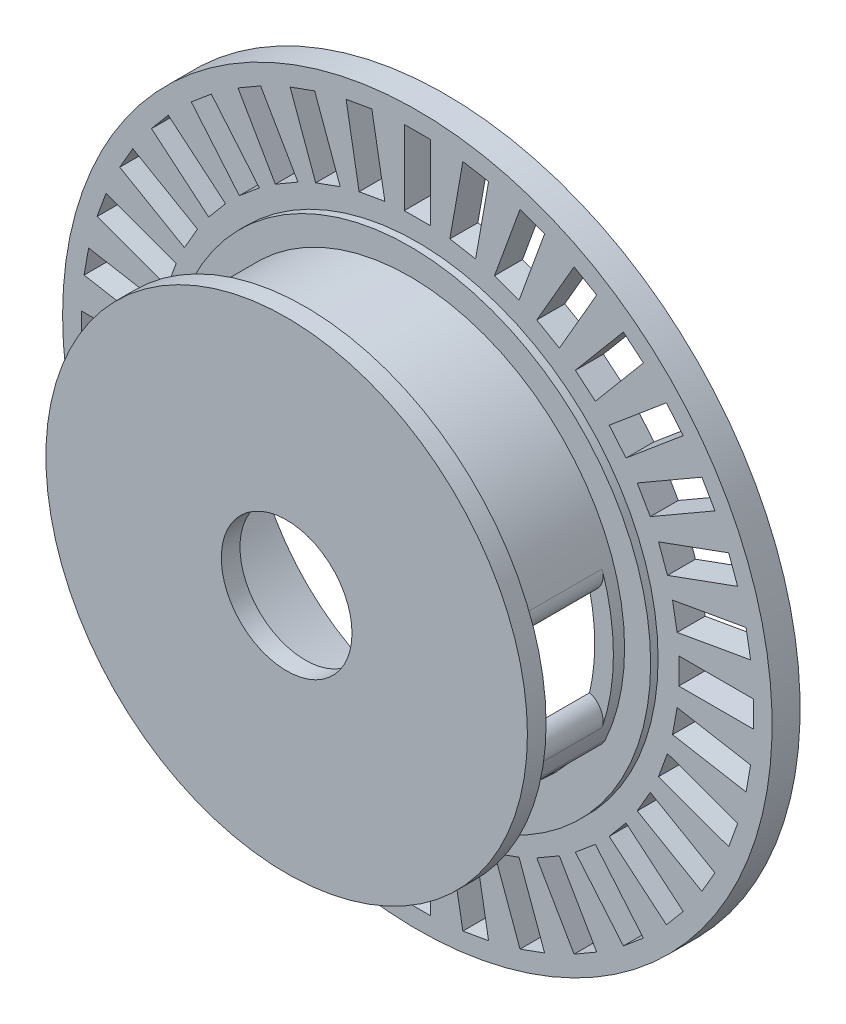
SolidWorks part; units mm, degrees
ref_plane "Front Plane" through (0, 0, 0) normal (0, 0, 1) x (1, 0, 0)
ref_plane "Top Plane" through (0, 0, 0) normal (0, 1, 0) x (1, 0, 0)
ref_plane "Right Plane" through (0, 0, 0) normal (1, 0, 0) x (0, 0, -1)
sketch "Sketch1" plane through (0, 0, 0) normal (0, 0, 1) x (1, 0, 0)
  line L0 (3.1204, 13.6658) -> (1.7417, 13.9089)
  line L1 (0.7, 14) -> (-0.7, 14)
  line L2 (0.7, 14) -> (0.7, 18)
  line L3 (0.7, 18) -> (-0.7, 18)
  line L4 (-0.7, 14) -> (-0.7, 18)
  line L5 (0.7, 14) -> (-0.7, 18) construction
  line L6 (0.7, 18) -> (-0.7, 14) construction
  line L7 (1.7417, 13.9089) -> (2.4363, 17.8481)
  line L8 (3.1204, 13.6658) -> (3.815, 17.605)
  line L9 (3.815, 17.605) -> (2.4363, 17.8481)
  line L10 (5.4461, 12.9163) -> (4.1305, 13.3951)
  line L11 (4.1305, 13.3951) -> (5.4986, 17.1539)
  line L12 (5.4461, 12.9163) -> (6.8141, 16.6751)
  line L13 (6.8141, 16.6751) -> (5.4986, 17.1539)
  line L14 (7.6062, 11.7744) -> (6.3938, 12.4744)
  line L15 (6.3938, 12.4744) -> (8.3938, 15.9385)
  line L16 (7.6062, 11.7744) -> (9.6062, 15.2385)
  line L17 (9.6062, 15.2385) -> (8.3938, 15.9385)
  line L18 (9.5353, 10.2747) -> (8.4628, 11.1746)
  line L19 (8.4628, 11.1746) -> (11.0339, 14.2388)
  line L20 (9.5353, 10.2747) -> (12.1064, 13.3388)
  line L21 (12.1064, 13.3388) -> (11.0339, 14.2388)
  line L22 (11.1746, 8.4628) -> (10.2747, 9.5353)
  line L23 (10.2747, 9.5353) -> (13.3388, 12.1064)
  line L24 (11.1746, 8.4628) -> (14.2388, 11.0339)
  line L25 (14.2388, 11.0339) -> (13.3388, 12.1064)
  line L26 (12.4744, 6.3938) -> (11.7744, 7.6062)
  line L27 (11.7744, 7.6062) -> (15.2385, 9.6062)
  line L28 (12.4744, 6.3938) -> (15.9385, 8.3938)
  line L29 (15.9385, 8.3938) -> (15.2385, 9.6062)
  line L30 (13.3951, 4.1305) -> (12.9163, 5.4461)
  line L31 (12.9163, 5.4461) -> (16.6751, 6.8141)
  line L32 (13.3951, 4.1305) -> (17.1539, 5.4986)
  line L33 (17.1539, 5.4986) -> (16.6751, 6.8141)
  line L34 (13.9089, 1.7417) -> (13.6658, 3.1204)
  line L35 (13.6658, 3.1204) -> (17.605, 3.815)
  line L36 (13.9089, 1.7417) -> (17.8481, 2.4363)
  line L37 (17.8481, 2.4363) -> (17.605, 3.815)
  line L38 (14, -0.7) -> (14, 0.7)
  line L39 (14, 0.7) -> (18, 0.7)
  line L40 (14, -0.7) -> (18, -0.7)
  line L41 (18, -0.7) -> (18, 0.7)
  line L42 (13.6658, -3.1204) -> (13.9089, -1.7417)
  line L43 (13.9089, -1.7417) -> (17.8481, -2.4363)
  line L44 (13.6658, -3.1204) -> (17.605, -3.815)
  line L45 (17.605, -3.815) -> (17.8481, -2.4363)
  line L46 (12.9163, -5.4461) -> (13.3951, -4.1305)
  line L47 (13.3951, -4.1305) -> (17.1539, -5.4986)
  line L48 (12.9163, -5.4461) -> (16.6751, -6.8141)
  line L49 (16.6751, -6.8141) -> (17.1539, -5.4986)
  line L50 (11.7744, -7.6062) -> (12.4744, -6.3938)
  line L51 (12.4744, -6.3938) -> (15.9385, -8.3938)
  line L52 (11.7744, -7.6062) -> (15.2385, -9.6062)
  line L53 (15.2385, -9.6062) -> (15.9385, -8.3938)
  line L54 (10.2747, -9.5353) -> (11.1746, -8.4628)
  line L55 (11.1746, -8.4628) -> (14.2388, -11.0339)
  line L56 (10.2747, -9.5353) -> (13.3388, -12.1064)
  line L57 (13.3388, -12.1064) -> (14.2388, -11.0339)
  line L58 (8.4628, -11.1746) -> (9.5353, -10.2747)
  line L59 (9.5353, -10.2747) -> (12.1064, -13.3388)
  line L60 (8.4628, -11.1746) -> (11.0339, -14.2388)
  line L61 (11.0339, -14.2388) -> (12.1064, -13.3388)
  line L62 (6.3938, -12.4744) -> (7.6062, -11.7744)
  line L63 (7.6062, -11.7744) -> (9.6062, -15.2385)
  line L64 (6.3938, -12.4744) -> (8.3938, -15.9385)
  line L65 (8.3938, -15.9385) -> (9.6062, -15.2385)
  line L66 (4.1305, -13.3951) -> (5.4461, -12.9163)
  line L67 (5.4461, -12.9163) -> (6.8141, -16.6751)
  line L68 (4.1305, -13.3951) -> (5.4986, -17.1539)
  line L69 (5.4986, -17.1539) -> (6.8141, -16.6751)
  line L70 (1.7417, -13.9089) -> (3.1204, -13.6658)
  line L71 (3.1204, -13.6658) -> (3.815, -17.605)
  line L72 (1.7417, -13.9089) -> (2.4363, -17.8481)
  line L73 (2.4363, -17.8481) -> (3.815, -17.605)
  line L74 (-0.7, -14) -> (0.7, -14)
  line L75 (0.7, -14) -> (0.7, -18)
  line L76 (-0.7, -14) -> (-0.7, -18)
  line L77 (-0.7, -18) -> (0.7, -18)
  line L78 (-3.1204, -13.6658) -> (-1.7417, -13.9089)
  line L79 (-1.7417, -13.9089) -> (-2.4363, -17.8481)
  line L80 (-3.1204, -13.6658) -> (-3.815, -17.605)
  line L81 (-3.815, -17.605) -> (-2.4363, -17.8481)
  line L82 (-5.4461, -12.9163) -> (-4.1305, -13.3951)
  line L83 (-4.1305, -13.3951) -> (-5.4986, -17.1539)
  line L84 (-5.4461, -12.9163) -> (-6.8141, -16.6751)
  line L85 (-6.8141, -16.6751) -> (-5.4986, -17.1539)
  line L86 (-7.6062, -11.7744) -> (-6.3938, -12.4744)
  line L87 (-6.3938, -12.4744) -> (-8.3938, -15.9385)
  line L88 (-7.6062, -11.7744) -> (-9.6062, -15.2385)
  line L89 (-9.6062, -15.2385) -> (-8.3938, -15.9385)
  line L90 (-9.5353, -10.2747) -> (-8.4628, -11.1746)
  line L91 (-8.4628, -11.1746) -> (-11.0339, -14.2388)
  line L92 (-9.5353, -10.2747) -> (-12.1064, -13.3388)
  line L93 (-12.1064, -13.3388) -> (-11.0339, -14.2388)
  line L94 (-11.1746, -8.4628) -> (-10.2747, -9.5353)
  line L95 (-10.2747, -9.5353) -> (-13.3388, -12.1064)
  line L96 (-11.1746, -8.4628) -> (-14.2388, -11.0339)
  line L97 (-14.2388, -11.0339) -> (-13.3388, -12.1064)
  line L98 (-12.4744, -6.3938) -> (-11.7744, -7.6062)
  line L99 (-11.7744, -7.6062) -> (-15.2385, -9.6062)
  line L100 (-12.4744, -6.3938) -> (-15.9385, -8.3938)
  line L101 (-15.9385, -8.3938) -> (-15.2385, -9.6062)
  line L102 (-13.3951, -4.1305) -> (-12.9163, -5.4461)
  line L103 (-12.9163, -5.4461) -> (-16.6751, -6.8141)
  line L104 (-13.3951, -4.1305) -> (-17.1539, -5.4986)
  line L105 (-17.1539, -5.4986) -> (-16.6751, -6.8141)
  line L106 (-13.9089, -1.7417) -> (-13.6658, -3.1204)
  line L107 (-13.6658, -3.1204) -> (-17.605, -3.815)
  line L108 (-13.9089, -1.7417) -> (-17.8481, -2.4363)
  line L109 (-17.8481, -2.4363) -> (-17.605, -3.815)
  line L110 (-14, 0.7) -> (-14, -0.7)
  line L111 (-14, -0.7) -> (-18, -0.7)
  line L112 (-14, 0.7) -> (-18, 0.7)
  line L113 (-18, 0.7) -> (-18, -0.7)
  line L114 (-13.6658, 3.1204) -> (-13.9089, 1.7417)
  line L115 (-13.9089, 1.7417) -> (-17.8481, 2.4363)
  line L116 (-13.6658, 3.1204) -> (-17.605, 3.815)
  line L117 (-17.605, 3.815) -> (-17.8481, 2.4363)
  line L118 (-12.9163, 5.4461) -> (-13.3951, 4.1305)
  line L119 (-13.3951, 4.1305) -> (-17.1539, 5.4986)
  line L120 (-12.9163, 5.4461) -> (-16.6751, 6.8141)
  line L121 (-16.6751, 6.8141) -> (-17.1539, 5.4986)
  line L122 (-11.7744, 7.6062) -> (-12.4744, 6.3938)
  line L123 (-12.4744, 6.3938) -> (-15.9385, 8.3938)
  line L124 (-11.7744, 7.6062) -> (-15.2385, 9.6062)
  line L125 (-15.2385, 9.6062) -> (-15.9385, 8.3938)
  line L126 (-10.2747, 9.5353) -> (-11.1746, 8.4628)
  line L127 (-11.1746, 8.4628) -> (-14.2388, 11.0339)
  line L128 (-10.2747, 9.5353) -> (-13.3388, 12.1064)
  line L129 (-13.3388, 12.1064) -> (-14.2388, 11.0339)
  line L130 (-8.4628, 11.1746) -> (-9.5353, 10.2747)
  line L131 (-9.5353, 10.2747) -> (-12.1064, 13.3388)
  line L132 (-8.4628, 11.1746) -> (-11.0339, 14.2388)
  line L133 (-11.0339, 14.2388) -> (-12.1064, 13.3388)
  line L134 (-6.3938, 12.4744) -> (-7.6062, 11.7744)
  line L135 (-7.6062, 11.7744) -> (-9.6062, 15.2385)
  line L136 (-6.3938, 12.4744) -> (-8.3938, 15.9385)
  line L137 (-8.3938, 15.9385) -> (-9.6062, 15.2385)
  line L138 (-4.1305, 13.3951) -> (-5.4461, 12.9163)
  line L139 (-5.4461, 12.9163) -> (-6.8141, 16.6751)
  line L140 (-4.1305, 13.3951) -> (-5.4986, 17.1539)
  line L141 (-5.4986, 17.1539) -> (-6.8141, 16.6751)
  line L142 (-1.7417, 13.9089) -> (-3.1204, 13.6658)
  line L143 (-3.1204, 13.6658) -> (-3.815, 17.605)
  line L144 (-1.7417, 13.9089) -> (-2.4363, 17.8481)
  line L145 (-2.4363, 17.8481) -> (-3.815, 17.605)
  circle A0 centre (0, 0) radius 19
  circle A1 centre (0, 0) radius 3.4
  point P3 (0, 16)
  dimension "D2" = 38
  dimension "D5" = 6.8
  dimension "D1" = 1.4
  dimension "D3" = 4
  dimension "D6" = 18
  dimension "D4" = 36
extrude "Boss-Extrude1" add sketch "Sketch1" along normal blind 1.5
sketch "Sketch2" [suppressed] plane through (0, 0, 1.2) normal (0, 0, 1) x (1, 0, 0)
  circle A0 centre (0, 0) radius 6.4
  circle A1 centre (0, 0) radius 3.4
  circle A2 centre (0, 0) radius 6.25 construction
  circle A4 centre (0, 0) radius 3.4 construction
  dimension "D1" = 3
  dimension "D3" = 12.5
sketch "Sketch3" plane through (0, 0, 1.5) normal (0, 0, 1) x (1, 0, 0)
  circle A0 centre (0, 0) radius 3.4
  circle A1 centre (0, 0) radius 11.5
  circle A3 centre (0, 0) radius 3.4 construction
  dimension "D1" = 23
extrude "Boss-Extrude3" add sketch "Sketch3" along normal blind 1
sketch "Sketch4" plane through (0, 0, 2.5) normal (0, 0, 1) x (1, 0, 0)
  line L1 (7.858, -2.4) -> (13.142, -2.4)
  line L2 (7.858, -2.4) -> (7.858, 2.4)
  line L3 (7.858, 2.4) -> (13.142, 2.4)
  line L4 (13.142, -2.4) -> (13.142, 2.4)
  line L5 (7.858, -2.4) -> (13.142, 2.4) construction
  line L6 (7.858, 2.4) -> (13.142, -2.4) construction
  circle A0 centre (0, 0) radius 11.5
  circle A1 centre (0, 0) radius 10.5
  circle A2 centre (0, 0) radius 11.5 construction
  point P6 (10.5, 0)
  circle M2 centre (0, 0) radius 11.5
  dimension "D1" = 1
  dimension "D2" = 4.8
extrude "Boss-Extrude4" add sketch "Sketch4" along normal blind 6 contours A1 L3 L1 M2 region at (10.7344, -2.7235, 2.5)
ref_plane "Plane2" through (0, 0, 3) normal (0, 0, 1) x (1, 0, 0)
sketch "Sketch5" plane through (0, 0, 1.5) normal (0, 0, 1) x (1, 0, 0)
  line L0 (0, 0) -> (15.9926, 9.2333)
  line L1 (15.9926, 9.2333) -> (12.4926, 15.2955)
  line L2 (12.4926, 15.2955) -> (-1.9963, 6.9303)
  line L3 (-1.9963, 6.9303) -> (0, 0)
  line L4 (0, 0) -> (19.351, 0) construction
  line L5 (-1.9963, -6.9303) -> (0, 0)
  line L6 (12.4926, -15.2955) -> (-1.9963, -6.9303)
  line L7 (15.9926, -9.2333) -> (12.4926, -15.2955)
  line L8 (0, 0) -> (15.9926, -9.2333)
  circle A0 centre (0, 0) radius 10.5
  circle A1 centre (0, 0) radius 13.5
  arc A2 (10.222, 2.4) -> (10.222, -2.4) centre (0, 0) ccw construction
  dimension "D1" = 7
  dimension "D2" = 30
extrude "Cut-Extrude1" cut sketch "Sketch5" along normal blind 5 contours L6 A1 L8 A0 region at (7.9073, -8.7463, 1.5)
fillet "Fillet1" radius 1 2 edges at (11.2468, 2.4, 5.5) (11.2468, -2.4, 5.5)
sketch "Sketch6" plane through (0, 0, 0) normal (1, 0, 0) x (0, 0, -1)
  line L0 (-1.5, 19) -> (-1.5, -19) construction
  line L1 (-6.8276, -6.4) -> (-1.5, -6.4)
  line L2 (-6.8276, -6.4) -> (-6.8276, 6.4)
  line L3 (-6.8276, 6.4) -> (-1.5, 6.4)
  line L4 (-1.5, -6.4) -> (-1.5, 6.4)
  line L5 (-6.8276, -6.4) -> (-1.5, 6.4) construction
  line L6 (-6.8276, 6.4) -> (-1.5, -6.4) construction
  circle A0 centre (-4.1638, 0) radius 0.75
  point P2 (-4.1638, 0)
  dimension "D1" = 1.5
extrude "Cut-Extrude2" cut sketch "Sketch6" against normal blind 22 and the other way blind 4 contours A0 region at (0, 0, 4.1638)
fillet "Fillet2" radius 1 1 edges at (9.9593, -5.75, 4)
sketch "Sketch10" plane through (0, 0, 0) normal (0, 1, 0) x (1, 0, 0)
  line L0 (-11.5, -4.7001) -> (-17.7584, -4.7001) construction
  line L10 (12.8947, -0.9002) -> (12.8947, -1.9002)
  line L11 (10.8947, -8.5) -> (12.8947, -8.5)
  line L12 (10.8947, -8.5) -> (10.8947, -7.5)
  line L13 (10.8947, -7.5) -> (12.8947, -7.5)
  line L14 (12.8947, -8.5) -> (12.8947, -7.5)
  line L15 (10.8947, -1.9002) -> (12.8947, -1.9002)
  line L16 (10.8947, -0.9002) -> (10.8947, -1.9002)
  line L17 (10.8947, -0.9002) -> (12.8947, -0.9002)
  line L18 (12.8947, 0) -> (12.8947, -5.1753) construction
  line L19 (19, 0) -> (-19, 0) construction
  line L21 (0, 0) -> (0, 9.3712) construction
  line L22 (10.8947, -2.5) -> (10.8947, -8.5) construction
  dimension "D1" = 1
  dimension "D2" = 2
revolve "Revolve1" add sketch "Sketch10" angle 360 about L21
mirror "Mirror3" about plane through (0, 0, 0) normal (0, 0, 1) of bodies 109 111
sketch "Sketch15" plane through (0, 0, 8.5) normal (0, 0, 1) x (1, 0, 0)
  circle A0 centre (0, 0) radius 10.5
  dimension "D1" = 21
extrude "Cut-Extrude8" cut sketch "Sketch15" against normal blind 20
sketch "Sketch16" plane through (0, 0, 0) normal (0, 0, 1) x (1, 0, 0)
  circle A0 centre (0, 0) radius 19
extrude "Cut-Extrude9" cut sketch "Sketch16" against normal blind 12.2
sketch "Sketch18" plane through (0, 0, 0) normal (1, 0, 0) x (0, 0, -1)
  line L1 (-2.5, 2.4) -> (-7.2, 2.4)
  line L2 (-2.5, 2.4) -> (-2.5, -2.4)
  line L3 (-2.5, -2.4) -> (-7.2, -2.4)
  line L4 (-7.2, 2.4) -> (-7.2, -2.4)
  line L6 (-2.2001, -5.3611) -> (-2.2001, -7.2185)
  line L7 (-2.2001, -7.2185) -> (-7.2, -7.2185)
  line L8 (-7.2, -5.3611) -> (-7.2, -7.2185)
  line L9 (-8.5, -2.4) -> (-2.5, -2.4) construction
  line L11 (-7.2, -5.3611) -> (-2.2001, -5.3611)
  line L14 (-6.5, -5.3611) -> (-1.9002, -5.3611) construction
extrude "Cut-Extrude10" cut sketch "Sketch18" along normal blind 18
sketch "Sketch19" [suppressed] plane through (0, 0, 7.2001) normal (0, 0, -1) x (-1, 0, 0)
  line L0 (0, 0) -> (-21.0954, 2.1808)
  line L1 (0, 0) -> (-17.679, 16.2571)
  circle A0 centre (0, 0) radius 11.5
  circle A1 centre (0, 0) radius 14
  dimension "D1" = 28
  dimension "D2" = 23
extrude "Cut-Extrude11" [suppressed] cut sketch "Sketch19" along normal blind 2 contours L1 A1 L0 A0
fillet "Fillet4" [suppressed] radius 10
sketch "Sketch20" plane through (0, 0, 8.5) normal (0, 0, 1) x (1, 0, 0)
  circle A0 centre (0, 0) radius 12.8947
  circle A1 centre (0, 0) radius 3.5
  circle A2 centre (0, 0) radius 12.8947 construction
  dimension "D1" = 7
extrude "Boss-Extrude5" add sketch "Sketch20" against normal blind 1
equation "\"|.6\"=1.2"
